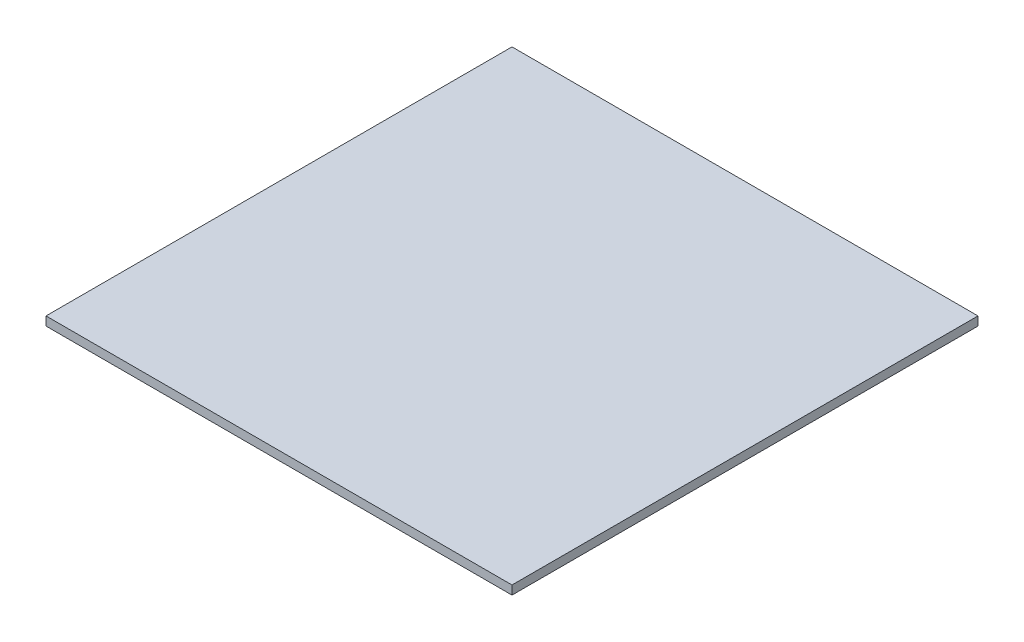
SolidWorks part; units mm, degrees
ref_plane "Front Plane" through (0, 0, 0) normal (0, 0, 1) x (1, 0, 0)
ref_plane "Top Plane" through (0, 0, 0) normal (0, 1, 0) x (1, 0, 0)
ref_plane "Right Plane" through (0, 0, 0) normal (1, 0, 0) x (0, 0, -1)
sketch "Sketch1" plane through (0, 0, 0) normal (0, 1, 0) x (1, 0, 0)
  line L1 (-63.5, -63.5) -> (63.5, -63.5)
  line L2 (-63.5, -63.5) -> (-63.5, 63.5)
  line L3 (-63.5, 63.5) -> (63.5, 63.5)
  line L4 (63.5, -63.5) -> (63.5, 63.5)
  line L5 (-63.5, -63.5) -> (63.5, 63.5) construction
  line L6 (-63.5, 63.5) -> (63.5, -63.5) construction
  point P0 (0, 0)
  dimension "D1" = 127
  dimension "D2" = 127
extrude "Boss-Extrude1" add sketch "Sketch1" along normal blind 2.4
